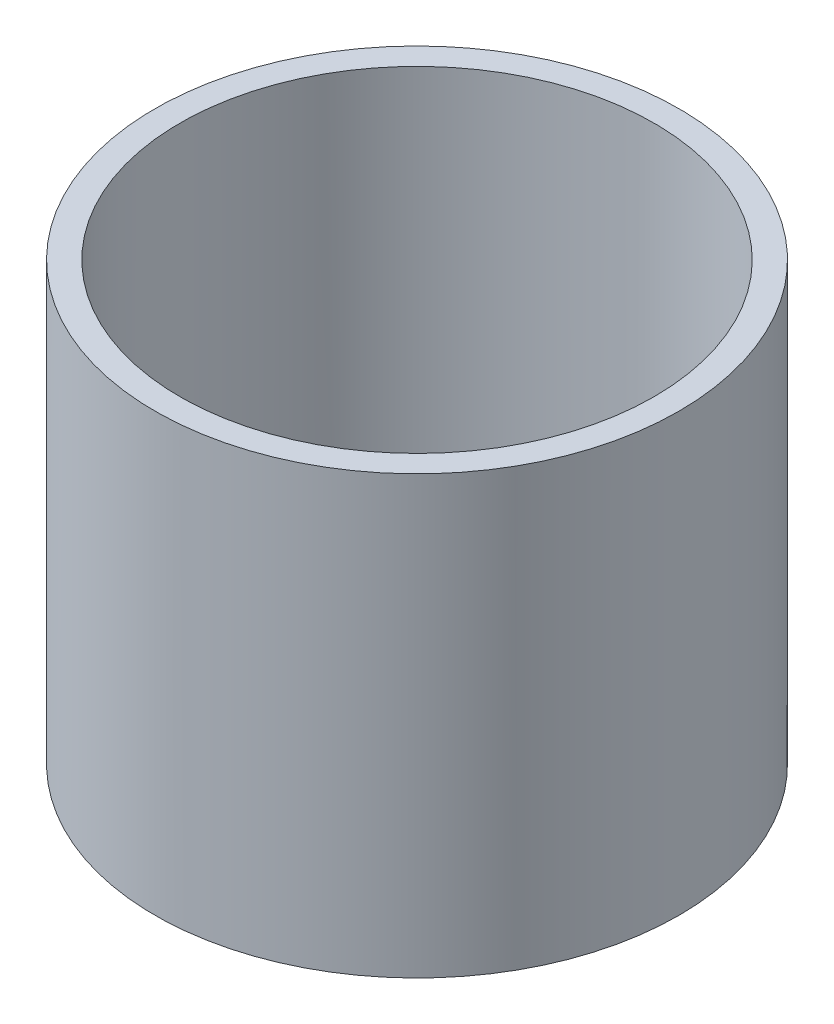
SolidWorks part; units mm, degrees
ref_plane "Front Plane" through (0, 0, 0) normal (0, 0, 1) x (1, 0, 0)
ref_plane "Top Plane" through (0, 0, 0) normal (0, 1, 0) x (1, 0, 0)
ref_plane "Right Plane" through (0, 0, 0) normal (1, 0, 0) x (0, 0, -1)
sketch "Sketch2" plane through (0, 0, 0) normal (0, 0, 1) x (1, 0, 0)
  line L0 (21, 35) -> (21, 0)
  line L1 (21, 0) -> (6.5, -5.2776)
  line L2 (6.5, -5.2776) -> (4.5, -5.2776)
  line L3 (4.5, -5.2776) -> (19, 0)
  line L4 (19, 0) -> (19, 35)
  line L5 (19, 35) -> (21, 35)
  line L6 (0, -1000) -> (0, 49000) construction
  line L7 (4.5, -5.2776) -> (10.3857, -5.2776) construction
  dimension "D1" = 2
  dimension "D2" = 35
  dimension "D3" = 20
  dimension "D4" = 19
  dimension "D5" = 4.5
revolve "Revolve2" add sketch "Sketch2" angle 360 about L6
